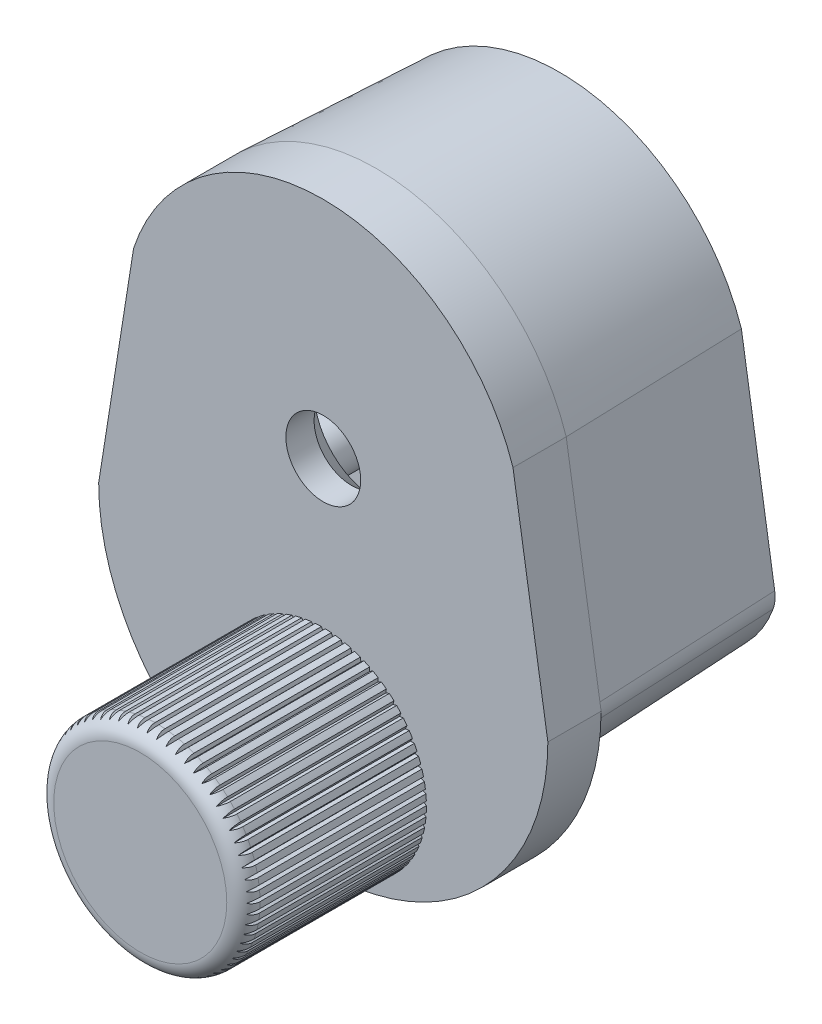
SolidWorks part; units mm, degrees
material "PET"
ref_plane "Спереди" through (0, 0, 0) normal (0, 0, 1) x (1, 0, 0)
ref_plane "Сверху" through (0, 0, 0) normal (0, 1, 0) x (1, 0, 0)
ref_plane "Справа" through (0, 0, 0) normal (1, 0, 0) x (0, 0, -1)
sketch "Эскиз1" plane through (0, 0, 0) normal (0, 0, 1) x (1, 0, 0)
  line L0 (0, 0) -> (0, 9.5) construction
  line L1 (-11.4036, 13.2359) -> (-13.5, 0)
  line L2 (13.5, 0) -> (11.4036, 13.2359)
  arc A0 (-13.5, 0) -> (13.5, 0) centre (0, 0) ccw
  arc A1 (11.4036, 13.2359) -> (-11.4036, 13.2359) centre (0, 9.5) ccw
  dimension "D1" = 27
  dimension "D2" = 24
  dimension "D3" = 35
  dimension "D4" = 9
  dimension "D5" = 9
extrude "Бобышка-Вытянуть1" add sketch "Эскиз1" along normal blind 3.2
sketch "Эскиз2" plane through (0, 0, 3.2) normal (0, 0, 1) x (1, 0, 0)
  line L0 (0, -7) -> (0, 0) construction
  circle A0 centre (0, -7) radius 6.2
  dimension "D1" = 12.4
  dimension "D2" = 7
extrude "Бобышка-Вытянуть2" add sketch "Эскиз2" along normal blind 11
fillet "Скругление1" radius 1 1 edges at (6.2, -7, 14.2)
sketch "Эскиз3" plane through (0, 0, 14.2) normal (0, 0, 1) x (1, 0, 0)
  line L0 (-0.1149, -0.8011) -> (0, -1)
  line L1 (0, -0.8) -> (0, -1) construction
  line L2 (0.1149, -0.8011) -> (0, -1)
  arc A0 (0.1149, -0.8011) -> (-0.1149, -0.8011) centre (0, -7) ccw
  circle A1 centre (0, -7) radius 6.2 construction
  dimension "D1" = 0.2
  dimension "D2" = 60
extrude "Вырез-Вытянуть1" cut sketch "Эскиз3" against normal blind 11
pattern_circular "Круговой массив1" count 65 over 360 about axis through (0, -7, 13.2) along (0, 0, -1) of "Вырез-Вытянуть1"
sketch "Эскиз4" plane through (0, 0, 0) normal (0, 0, -1) x (-1, 0, 0)
  line L0 (0, -7) -> (0, 8) construction
  circle A0 centre (0, -7) radius 3
  circle A1 centre (0, 8) radius 2.25
  dimension "D1" = 6
  dimension "D2" = 4.5
  dimension "D3" = 15
extrude "Вырез-Вытянуть2" cut sketch "Эскиз4" against normal blind 4
chamfer "Фаска1" distance 1.5 angle 45 1 edges at (-2.25, 8, 0)
sketch "Эскиз5" plane through (0, 0, 0) normal (0, 0, -1) x (-1, 0, 0)
  line L0 (-17.323, -5.5) -> (19.629, -5.5) construction
  line L1 (0, 0) -> (0, 21.5) construction
  line L2 (-11.4036, 13.2359) -> (-13.5, 0)
  line L3 (13.5, 0) -> (11.4036, 13.2359)
  line L4 (-11.4036, 13.2359) -> (-13.5, 0)
  line L5 (13.5, 0) -> (11.4036, 13.2359)
  line L6 (0, 0) -> (-13.5, 0) construction
  line L7 (9.5, 0) -> (7.5, 12.3)
  line L8 (-7.5, 12.3) -> (-9.5, 0)
  line L9 (-6.5, -3.2171) -> (-9.5, 0)
  line L10 (-7.5645, -5.5) -> (-6.5, -3.2171)
  line L11 (-7.5, 12.3) -> (7.5, 12.3) construction
  line L12 (0, 0) -> (0, 12.3) construction
  line L13 (-0.0006, 0) -> (13.5, 0) construction
  line L14 (6.5, -3.2171) -> (9.5, 0)
  line L15 (7.5645, -5.5) -> (6.5, -3.2171)
  arc A0 (-13.5, 0) -> (-7.5645, -5.5) centre (-6.24, 1.8821) ccw
  arc A1 (13.5, 0) -> (7.5645, -5.5) centre (6.24, 1.8821) cw
  arc A2 (11.4036, 13.2359) -> (-11.4036, 13.2359) centre (0, 9.5) ccw
  arc A3 (-13.5, 0) -> (13.5, 0) centre (0, 0) ccw
  arc A4 (11.4036, 13.2359) -> (-11.4036, 13.2359) centre (0, 9.5) ccw
  arc A10 (7.5, 12.3) -> (-7.5, 12.3) centre (0, 9.5161) ccw
  point P11 (9.4497, 0.004)
  point P14 (9.5, 0)
  point P18 (-9.5, 0)
  point P20 (0, 0)
  point P21 (0, 0)
  point P22 (0, 0)
  arc M7 (11.4036, 13.2359) -> (-11.4036, 13.2359) centre (0, 9.5) ccw
  line M8 (-11.4036, 13.2359) -> (-13.5, 0)
  arc M9 (-13.5, 0) -> (13.5, 0) centre (0, 0) ccw
  line M10 (13.5, 0) -> (11.4036, 13.2359)
  dimension "D2" = 27
  dimension "D5" = 8
  dimension "D6" = 12.3
  dimension "D10" = 7.5
  dimension "D3" = 4
  dimension "D4" = 15
  dimension "D7" = 47
  dimension "D8" = 112
  dimension "D9" = 3
  dimension "D1" = 0
extrude "Бобышка-Вытянуть3" add sketch "Эскиз5" along normal blind 11 draft 2.5 contours L8 A10 L7 M9 M10 M7 M8 region at (0, 21.1182, 0)
fillet "Скругление2" radius 1 4 edges at (6.7861, -3.2624, -5.5) (-6.7861, -3.2624, -5.5)
fillet "Скругление3" radius 2 4 edges at (9.7559, -0.0777, -5.5) (-9.7559, -0.0777, -5.5)
sketch "Эскиз6" plane through (0, 0, -11) normal (0, 0, -1) x (-1, 0, 0)
  line L0 (0, 8) -> (0, -13.5) construction
  circle A0 centre (-8.5, 0) radius 1.5
  circle A1 centre (8.5, 0) radius 1.5
  arc A2 (-13.5, 0) -> (13.5, 0) centre (0, 0) ccw construction
  arc A3 (11.4036, 13.2359) -> (-11.4036, 13.2359) centre (0, 9.5) ccw construction
  dimension "D1" = 3
  dimension "D3" = 14
  dimension "D2" = 23
extrude "Бобышка-Вытянуть4" add sketch "Эскиз6" against normal up to surface (11 mm away) up to face at (-3, -7, 0)
